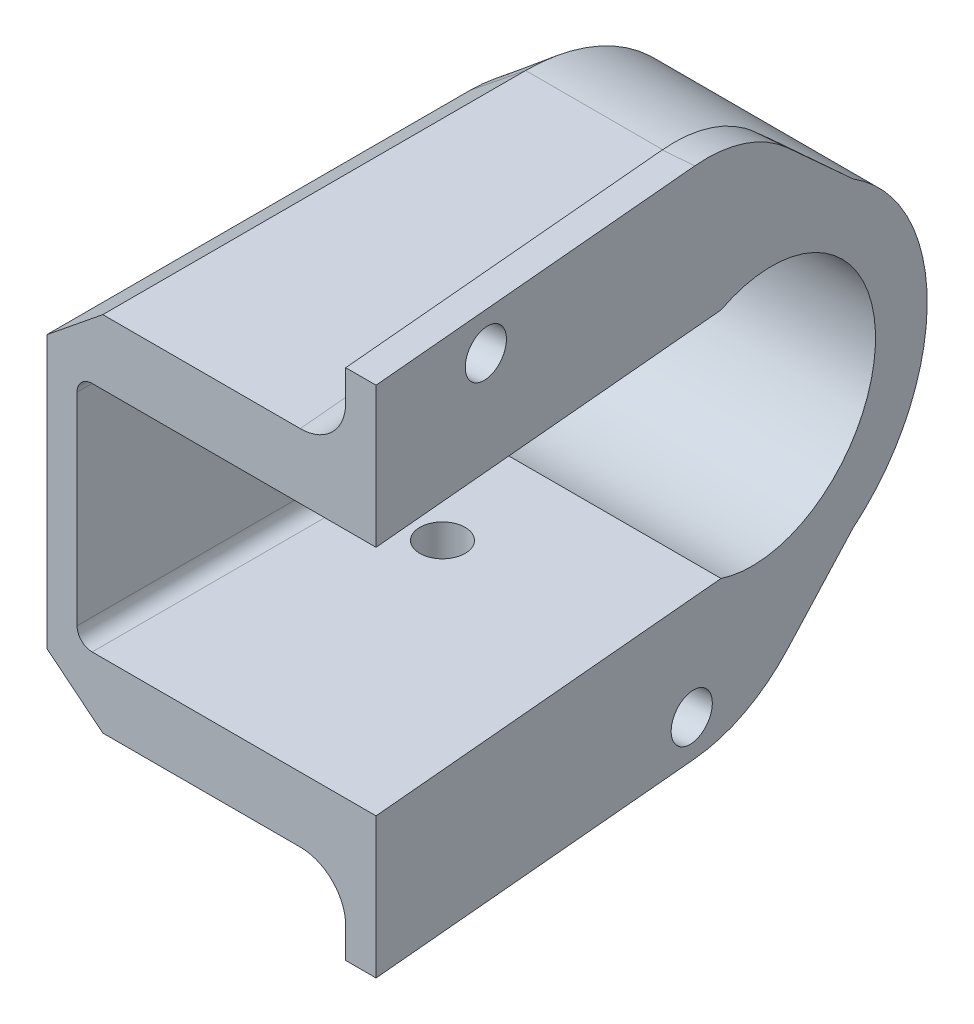
SolidWorks part; units mm, degrees
ref_plane "Front Plane" through (0, 0, 0) normal (0, 0, 1) x (1, 0, 0)
ref_plane "Top Plane" through (0, 0, 0) normal (0, 1, 0) x (1, 0, 0)
ref_plane "Right Plane" through (0, 0, 0) normal (1, 0, 0) x (0, 0, -1)
sketch "Sketch1" plane through (0, 0, 0) normal (1, 0, 0) x (0, 0, -1)
  line L0 (40, 12) -> (0, 12) construction
  line L1 (0, 0) -> (28, 0)
  line L2 (0, 0) -> (0, 24)
  line L3 (0, 24) -> (28, 24)
  arc A0 (28, 0) -> (28, 24) centre (28, 12) ccw
  dimension "D2" = 12
  dimension "D1" = 28
extrude "Face" add sketch "Sketch1" along normal blind 2
sketch "Sketch2" plane through (2, 0, 0) normal (1, 0, 0) x (0, 0, -1)
  line L0 (0, 24) -> (0, 19.7)
  line L1 (0, 24) -> (0, 0) construction
  line L5 (40, 12) -> (0, 12) construction
  line L9 (0, 19.7) -> (25.0382, 19.7)
  line L10 (0, 24) -> (28, 24)
  line L11 (0, 0) -> (28, 0)
  line L12 (0, 4.3) -> (25.0382, 4.3)
  line L13 (0, 0) -> (0, 4.3)
  arc A3 (28, 24) -> (28, 0) centre (28, 12) cw
  arc A5 (25.0382, 4.3) -> (25.0382, 19.7) centre (28, 12) ccw
  dimension "D1" = 16.5
  dimension "D2" = 40
  dimension "D4" = 7.7
extrude "Corpo" add sketch "Sketch2" along normal blind 20
sketch "Sketch3" plane through (0, 24, 0) normal (0, 1, 0) x (1, 0, 0)
  line L0 (21.8, 0) -> (18.3005, 40)
  line L1 (22, 0) -> (0, 0) construction
  line L2 (22, 40) -> (0, 40) construction
  line L3 (18.3005, 40) -> (22, 40)
  line L4 (22, 40) -> (22, 0)
  line L5 (22, 0) -> (21.8, 0)
  dimension "D1" = 0.2
  dimension "D2" = 5
extrude "Inclinação 5°" cut sketch "Sketch3" against normal through all
sketch "Sketch8" plane through (21.6344, 0, -1.8928) normal (0.9962, 0, -0.0872) x (-0.0872, 0, -0.9962)
  line L0 (-1.9, 24) -> (26.207, 24)
  line L1 (32.8529, 22.0084) -> (28.0775, 26.3777)
  line L2 (21.327, 29) -> (-1.9, 29)
  line L3 (-1.9, 29) -> (-1.9, 24)
  line L4 (-0.1743, 12) -> (39.8478, 12) construction
  line L5 (-0.1743, 19.7) -> (-0.1743, 4.3) construction
  line L6 (-1.9, -5) -> (-1.9, 0)
  line L7 (21.327, -5) -> (-1.9, -5)
  line L8 (32.8529, 1.9916) -> (28.0775, -2.3777)
  line L9 (-1.9, 0) -> (26.207, 0)
  arc A0 (26.207, 24) -> (32.8529, 22.0084) centre (26.207, 11.9158) cw
  arc A1 (28.0775, 26.3777) -> (21.327, 29) centre (21.327, 19) ccw
  arc A2 (28.0775, -2.3777) -> (21.327, -5) centre (21.327, 5) cw
  arc A3 (26.207, 0) -> (32.8529, 1.9916) centre (26.207, 12.0842) ccw
  ellipse E0 centre (26.207, 12) end of major axis (38.2528, 12) minor radius 12 (26.207, 0) -> (26.207, 24) ccw construction
  ellipse E1 centre (27.8935, 12) end of major axis (27.8935, 24) minor radius 11.9543 (27.8935, 0) -> (27.8935, 24) ccw construction
  dimension "D2" = 10
  dimension "D1" = 5
extrude "Abas" add sketch "Sketch8" against normal blind 2
fillet "Raios Externos 3mm" radius 3 4 edges at (18.5675, 0, -14) (17.0672, 0.4205, -31.149) (18.5675, 24, -14) (17.0672, 23.5795, -31.149)
sketch "Sketch9" plane through (0, 0, 0) normal (0, 0, 1) x (1, 0, 0)
  line L1 (-2.5102, 30.3092) -> (26.5678, 30.3092)
  line L2 (-2.5102, 30.3092) -> (-2.5102, -6.3092)
  line L3 (-2.5102, -6.3092) -> (26.5678, -6.3092)
  line L4 (26.5678, 30.3092) -> (26.5678, -6.3092)
extrude "Corte - Nivelamento" cut sketch "Sketch9" along normal through all
ref_plane "Plano Auxiliar" through (21.8336, 0, -1.9102) normal (0.9962, 0, -0.0872) x (-0.0872, 0, -0.9962)
sketch "Sketch10" plane through (21.8336, 0, -1.9102) normal (0.9962, 0, -0.0872) x (-0.0872, 0, -0.9962)
  line L1 (21.327, 29) -> (-1.725, 29) construction
  line L2 (-1.725, -5) -> (21.327, -5) construction
  line L3 (-1.9, 19.7) -> (-1.9, 29) construction
  circle A1 centre (21.1, -2.5) radius 1.5
  circle A2 centre (6.1, 26.5) radius 1.5
  dimension "D1" = 3
  dimension "D2" = 2.5
  dimension "D3" = 2.5
  dimension "D4" = 15
  dimension "D5" = 8
extrude "Furos de Fixação Ø3" cut sketch "Sketch10" against normal up to next
chamfer "Chanfro 3x51°" distance 3 angle 51 3 edges at (0, 24, -14) (0, 12, -40) (0, 0, -14) first distance on face at (0, 12, -17)
fillet "Raios Internos 1mm" radius 1 3 edges at (2, 19.7, -12.5191) (2, 4.3, -12.5191) (2, 12, -36.25)
sketch "Sketch13" plane through (0, 0, 0) normal (0, -1, 0) x (1, 0, 0)
  line L0 (0, -28) -> (0, 0) construction
  line L1 (3.7047, -40) -> (18.3005, -40) construction
  circle A0 centre (8.2, -18) radius 1.5
  dimension "D3" = 3
  dimension "D1" = 8.2
  dimension "D2" = 22
extrude "Furo de Fixação do Pot. Ø3" cut sketch "Sketch13" against normal up to next
